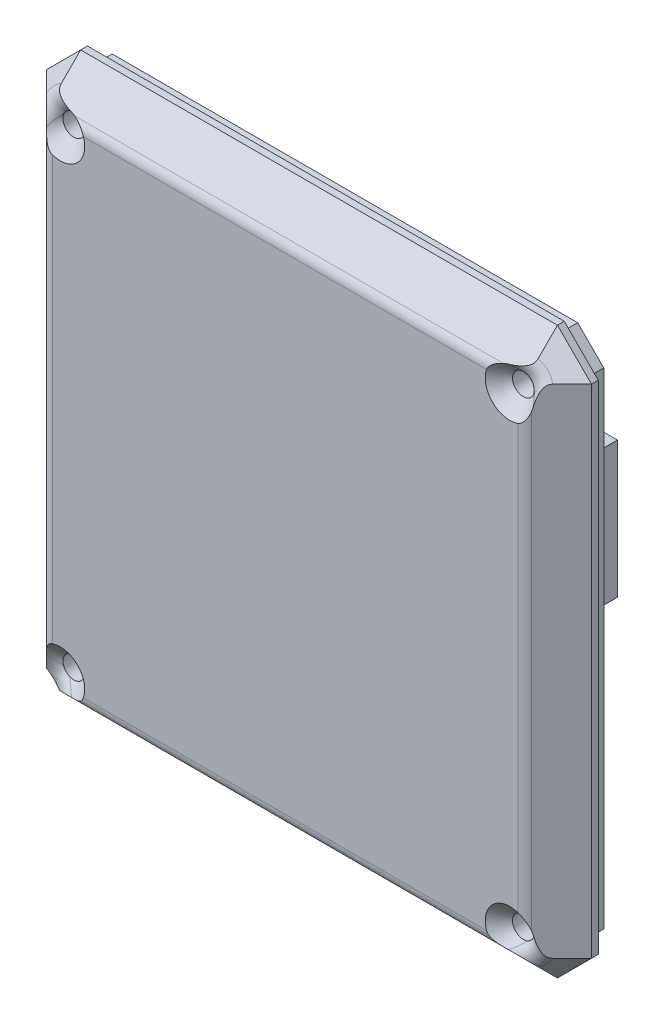
SolidWorks part; units mm, degrees
ref_plane "Front Plane" through (0, 0, 0) normal (0, 0, 1) x (1, 0, 0)
ref_plane "Top Plane" through (0, 0, 0) normal (0, 1, 0) x (1, 0, 0)
ref_plane "Right Plane" through (0, 0, 0) normal (1, 0, 0) x (0, 0, -1)
sketch "Sketch1" plane through (0, 0, 0) normal (0, 0, 1) x (1, 0, 0)
  line L1 (-40, 41.5) -> (40, 41.5)
  line L2 (-40, 41.5) -> (-40, -41.5)
  line L3 (-40, -41.5) -> (40, -41.5)
  line L4 (40, 41.5) -> (40, -41.5)
  point P6 (0, 41.5)
  point P7 (40, 0)
  dimension "D1" = 80
  dimension "D2" = 83
extrude "Boss-Extrude1" add sketch "Sketch1" along normal blind 6
chamfer "Chamfer1" distance 5 angle 45 8 edges at (0, 41.5, 6) (-40, 41.5, 3) (-40, 0, 6) (-40, -41.5, 3) (0, -41.5, 6) (40, -41.5, 3) (40, 0, 6) (40, 41.5, 3)
shell "Shell3" thickness 2 removed face at (0, 0, 0)
sketch "Sketch2" plane through (0, 0, 0) normal (0, 0, -1) x (-1, 0, 0)
  line L0 (-40, 36.5) -> (-35, 41.5) construction
  line L1 (-35, 41.5) -> (35, 41.5) construction
  line L2 (35, 41.5) -> (40, 36.5) construction
  line L3 (40, 36.5) -> (40, -36.5) construction
  line L4 (40, -36.5) -> (35, -41.5) construction
  line L5 (35, -41.5) -> (-35, -41.5) construction
  line L6 (-35, -41.5) -> (-40, -36.5) construction
  line L7 (-40, -36.5) -> (-40, 36.5) construction
  line L8 (-38, -35.6716) -> (-38, 35.6716)
  line L9 (-38, 35.6716) -> (-34.1716, 39.5)
  line L10 (-34.1716, 39.5) -> (34.1716, 39.5)
  line L11 (34.1716, 39.5) -> (38, 35.6716)
  line L12 (38, 35.6716) -> (38, -35.6716)
  line L13 (38, -35.6716) -> (34.1716, -39.5)
  line L14 (34.1716, -39.5) -> (-34.1716, -39.5)
  line L15 (-34.1716, -39.5) -> (-38, -35.6716)
  line L16 (-36, -34.8431) -> (-36, 34.8431)
  line L17 (-36, 34.8431) -> (-33.3431, 37.5)
  line L18 (-33.3431, 37.5) -> (33.3431, 37.5)
  line L19 (33.3431, 37.5) -> (36, 34.8431)
  line L20 (36, 34.8431) -> (36, -34.8431)
  line L21 (36, -34.8431) -> (33.3431, -37.5)
  line L22 (33.3431, -37.5) -> (-33.3431, -37.5)
  line L23 (-33.3431, -37.5) -> (-36, -34.8431)
  dimension "D1" = 2
  dimension "D2" = 2
extrude "Boss-Extrude2" add sketch "Sketch2" along normal blind 2.8 and the other way up to body separate body
sketch "Sketch4" plane through (0, 0, 4) normal (0, 0, -1) x (-1, 0, 0)
  line L0 (-36, 34.8431) -> (-36, -34.8431) construction
  line L1 (-36, 29.5) -> (-34, 29.5)
  line L2 (-36, 29.5) -> (-36, 35.5)
  line L3 (-34, 37.5) -> (-28, 37.5)
  line L4 (-28, 35.5) -> (-28, 37.5)
  line L5 (33.3431, 37.5) -> (-33.3431, 37.5) construction
  line L6 (0, 3.3) -> (0, -3.3) construction
  line L7 (34, 37.5) -> (28, 37.5)
  line L8 (28, 35.5) -> (28, 37.5)
  line L9 (36, 29.5) -> (34, 29.5)
  line L10 (36, 29.5) -> (36, 35.5)
  line L11 (3.3, 0) -> (-3.3, 0) construction
  line L12 (-34, -37.5) -> (-28, -37.5)
  line L13 (-28, -35.5) -> (-28, -37.5)
  line L14 (-36, -29.5) -> (-34, -29.5)
  line L15 (-36, -29.5) -> (-36, -35.5)
  line L16 (36, -29.5) -> (36, -35.5)
  line L17 (36, -29.5) -> (34, -29.5)
  line L18 (28, -35.5) -> (28, -37.5)
  line L19 (34, -37.5) -> (28, -37.5)
  line L20 (-36, 35.5) -> (-34, 37.5)
  line L21 (36, 35.5) -> (34, 37.5)
  line L22 (36, -35.5) -> (34, -37.5)
  line L23 (-36, -35.5) -> (-34, -37.5)
  arc A0 (-34, 29.5) -> (-28, 35.5) centre (-34, 35.5) ccw
  arc A1 (34, 29.5) -> (28, 35.5) centre (34, 35.5) cw
  arc A2 (-34, -29.5) -> (-28, -35.5) centre (-34, -35.5) cw
  arc A3 (34, -29.5) -> (28, -35.5) centre (34, -35.5) ccw
  point P2 (-36, 37.5)
  point P12 (36, 37.5)
  point P20 (-36, -37.5)
  point P27 (36, -37.5)
  dimension "D3" = 6
  dimension "D1" = 8
  dimension "D2" = 8
extrude "Boss-Extrude3" add sketch "Sketch4" along normal through all
sketch "Sketch3" plane through (0, 0, 6) normal (0, 0, 1) x (1, 0, 0)
  line L0 (0, -3.3) -> (0, 3.3) construction
  line L1 (3.3, 0) -> (-3.3, 0) construction
  circle A0 centre (-33, 34.5) radius 1.6
  circle A1 centre (33, 34.5) radius 1.6
  circle A2 centre (33, -34.5) radius 1.6
  circle A3 centre (-33, -34.5) radius 1.6
  dimension "D3" = 3.2
  dimension "D1" = 33
  dimension "D2" = 34.5
extrude "Cut-Extrude1" cut sketch "Sketch3" against normal through all
chamfer "Chamfer2" distance 2 angle 45 4 edges at (31.4, 34.5, 6) (-34.6, -34.5, 6) (-31.4, 34.5, 6) (34.6, -34.5, 6)
sketch "Sketch6" plane through (0, 0, 4) normal (0, 0, -1) x (-1, 0, 0)
  line L0 (-36, 29.5) -> (-36, -29.5) construction
  line L1 (-36, 23.5) -> (-26, 23.5)
  line L2 (-36, 23.5) -> (-36, 3.5)
  line L3 (-36, 3.5) -> (-26, 3.5)
  line L4 (-26, 23.5) -> (-26, 3.5)
  line L5 (34.1716, 39.5) -> (-34.1716, 39.5) construction
  dimension "D1" = 16
  dimension "D2" = 20
  dimension "D3" = 10
extrude "Boss-Extrude4" add sketch "Sketch6" along normal offset from surface (12.8 mm away) 6 up to face at (-34.6, -34.5, -2.8) offset beyond the face yes
chamfer "Chamfer3" distance 2 angle 45 4 edges at (36, 13.5, -8.8) (31, 23.5, -8.8) (26, 13.5, -8.8) (31, 3.5, -8.8)
fillet "Fillet1" radius 2 4 edges
fillet "Fillet2" radius 2 4 edges at (35, 0, 6) (0, 36.5, 6) (-35, 0, 6) (0, -36.5, 6)
